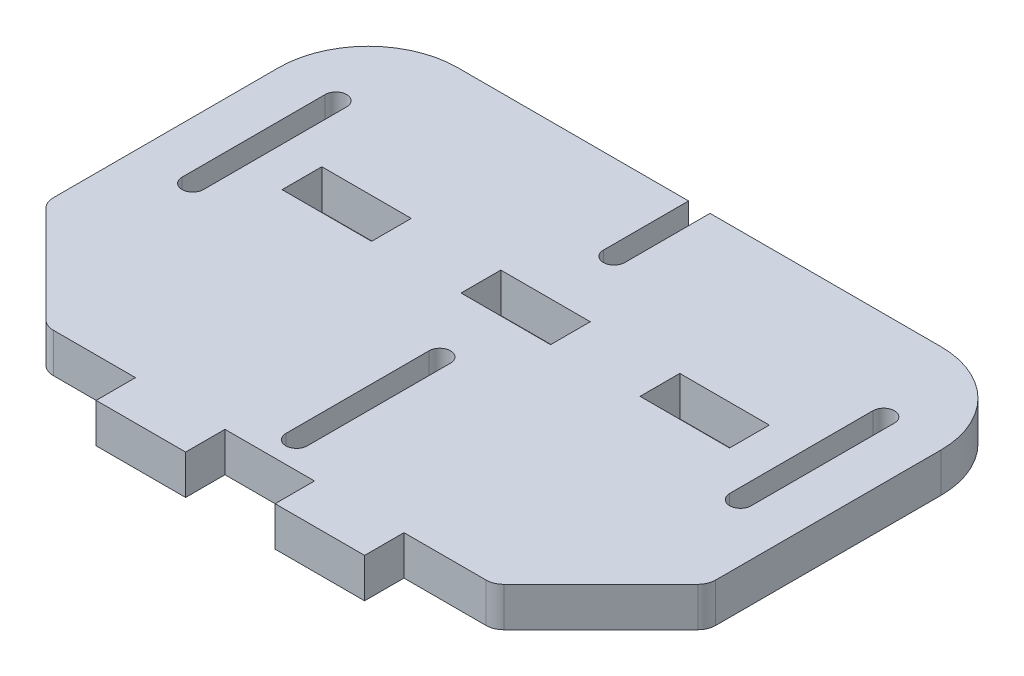
SolidWorks part; units mm, degrees
ref_plane "Front Plane" through (0, 0, 0) normal (0, 0, 1) x (1, 0, 0)
ref_plane "Top Plane" through (0, 0, 0) normal (0, 1, 0) x (1, 0, 0)
ref_plane "Right Plane" through (0, 0, 0) normal (1, 0, 0) x (0, 0, -1)
sketch "Sketch1" plane through (0, 0, 0) normal (0, 1, 0) x (1, 0, 0)
  line L8 (0, -7.5) -> (125, -7.5)
  line L12 (0, -7.5) -> (0, 3.5)
  line L14 (125, -7.5) -> (125, 3.5)
  line L17 (155, 33.5) -> (155, 123.5)
  line L18 (-30, 33.5) -> (-30, 123.5)
  line L23 (139, 58.5) -> (139, 98.5) construction
  line L24 (136, 58.5) -> (136, 98.5)
  line L25 (142, 58.5) -> (142, 98.5)
  line L26 (-14, 58.5) -> (-14, 98.5) construction
  line L27 (-17, 58.5) -> (-17, 98.5)
  line L28 (-11, 58.5) -> (-11, 98.5)
  line L29 (62.5, 11) -> (62.5, 51) construction
  line L30 (59.5, 11) -> (59.5, 51)
  line L31 (65.5, 11) -> (65.5, 51)
  line L32 (59.5, 123.5) -> (-30, 123.5)
  line L33 (65.5, 123.5) -> (65.5, 99.7057)
  line L34 (59.5, 123.5) -> (59.5, 99.7057)
  line L35 (155, 123.5) -> (65.5, 123.5)
  line L36 (125, 3.5) -> (155, 33.5)
  line L37 (0, 3.5) -> (-30, 33.5)
  arc A0 (136, 58.5) -> (142, 58.5) centre (139, 58.5) ccw
  arc A1 (142, 98.5) -> (136, 98.5) centre (139, 98.5) ccw
  arc A2 (-17, 58.5) -> (-11, 58.5) centre (-14, 58.5) ccw
  arc A3 (-11, 98.5) -> (-17, 98.5) centre (-14, 98.5) ccw
  arc A4 (59.5, 11) -> (65.5, 11) centre (62.5, 11) ccw
  arc A5 (65.5, 51) -> (59.5, 51) centre (62.5, 51) ccw
  arc A7 (59.5, 99.7057) -> (65.5, 99.7057) centre (62.5, 99.7057) ccw
  point P3 (0, 0)
  point P4 (-30, 78.5)
  point P5 (0, 0)
  point P6 (0, 0)
  point P10 (0, 0)
  point P13 (0, 0)
  point P14 (0, 0)
  point P18 (139, 78.5)
  point P23 (-14, 78.5)
  point P30 (62.5, 31)
  point P35 (-14, 55.5)
  point P36 (0, 0)
  point P37 (0, 0)
  point P38 (0, 0)
  point P40 (0, 0)
  dimension "D7" = 16
  dimension "D8" = 45
  dimension "D9" = 3
  dimension "D10" = 40
  dimension "D13" = 16
  dimension "D1" = 89.5
  dimension "D12" = 3
  dimension "D2" = 135
  dimension "D3" = 11
  dimension "D4" = 135
  dimension "D5" = 125
  dimension "D6" = 90
extrude "Boss-Extrude6" add sketch "Sketch1" along normal blind 11
sketch "Sketch4" plane through (0, 11, 0) normal (0, 1, 0) x (1, 0, 0)
  line L0 (0, -7.5) -> (125, -7.5) construction
  line L1 (0, -7.5) -> (25, -7.5)
  line L2 (0, -7.5) -> (0, 3.5)
  line L3 (0, 3.5) -> (25, 3.5)
  line L4 (25, -7.5) -> (25, 3.5)
  line L5 (50, -7.5) -> (75, -7.5)
  line L6 (50, -7.5) -> (50, 3.5)
  line L7 (50, 3.5) -> (75, 3.5)
  line L8 (75, -7.5) -> (75, 3.5)
  line L9 (0, 69.45) -> (25, 69.45)
  line L10 (125, -7.5) -> (100, -7.5)
  line L11 (125, -7.5) -> (125, 3.5)
  line L12 (125, 3.5) -> (100, 3.5)
  line L13 (100, -7.5) -> (100, 3.5)
  line L14 (0, 69.45) -> (0, 80.55)
  line L15 (0, 80.55) -> (25, 80.55)
  line L16 (25, 69.45) -> (25, 80.55)
  line L17 (50, 69.45) -> (75, 69.45)
  line L18 (50, 69.45) -> (50, 80.55)
  line L19 (50, 80.55) -> (75, 80.55)
  line L20 (75, 69.45) -> (75, 80.55)
  line L21 (125, 69.45) -> (100, 69.45)
  line L22 (125, 69.45) -> (125, 80.55)
  line L23 (125, 80.55) -> (100, 80.55)
  line L24 (100, 69.45) -> (100, 80.55)
  point P30 (125, 75)
  dimension "D1" = 25
  dimension "D2" = 25
  dimension "D3" = 25
  dimension "D4" = 25
  dimension "D5" = 82.5
  dimension "D6" = 11.1
extrude "Cut-Extrude1" cut sketch "Sketch4" against normal through all
fillet "Fillet1" radius 25 2 edges at (155, 5.5, -123.5) (-30, 5.5, -123.5)
fillet "Fillet2" radius 5 4 edges at (155, 5.5, -33.5) (125, 5.5, -3.5) (0, 5.5, -3.5) (-30, 5.5, -33.5)
